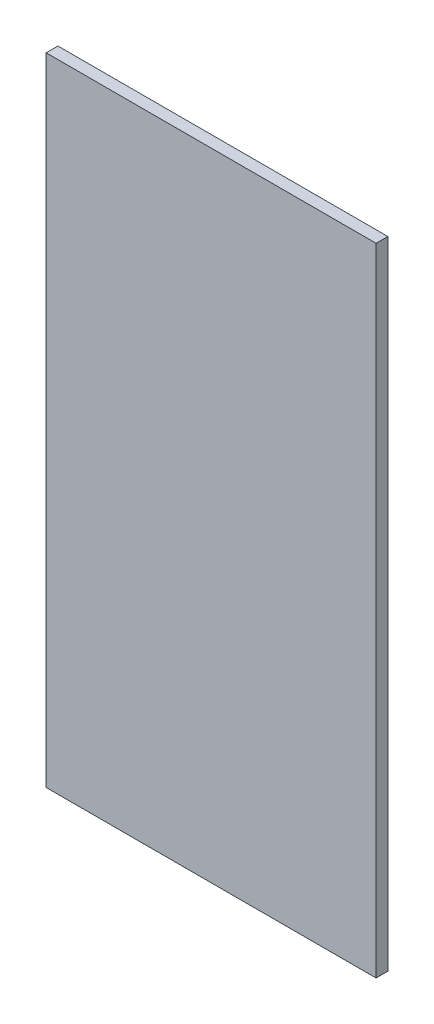
SolidWorks part; units mm, degrees
ref_plane "Front Plane" through (0, 0, 0) normal (0, 0, 1) x (1, 0, 0)
ref_plane "Top Plane" through (0, 0, 0) normal (0, 1, 0) x (1, 0, 0)
ref_plane "Right Plane" through (0, 0, 0) normal (1, 0, 0) x (0, 0, -1)
sketch "Sketch1" plane through (0, 0, 0) normal (0, 0, 1) x (1, 0, 0)
  line L1 (-25.4, 19.05) -> (152.4, 19.05)
  line L2 (-25.4, 19.05) -> (-25.4, -323.85)
  line L3 (-25.4, -323.85) -> (152.4, -323.85)
  line L4 (152.4, 19.05) -> (152.4, -323.85)
  dimension "D1" = 342.9
  dimension "D2" = 177.8
extrude "Boss-Extrude1" add sketch "Sketch1" along normal blind 6.35
